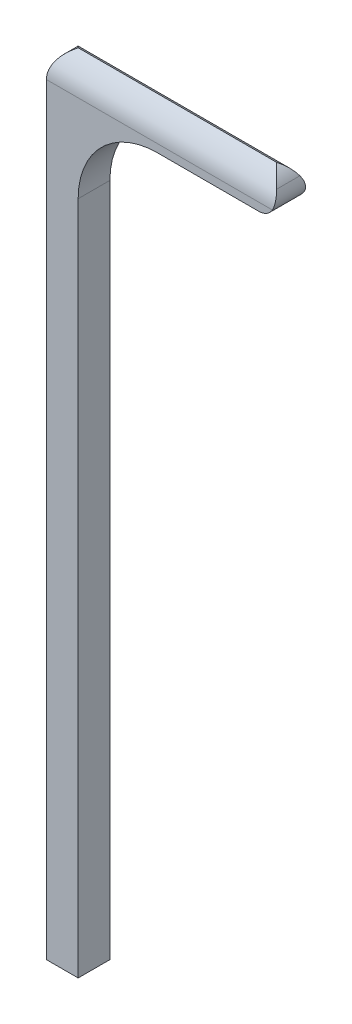
SolidWorks part; units mm, degrees
ref_plane "Front Plane" through (0, 0, 0) normal (0, 0, 1) x (1, 0, 0)
ref_plane "Top Plane" through (0, 0, 0) normal (0, 1, 0) x (1, 0, 0)
ref_plane "Right Plane" through (0, 0, 0) normal (1, 0, 0) x (0, 0, -1)
sketch "Sketch1" plane through (0, 0, 0) normal (0, 1, 0) x (1, 0, 0)
  line L1 (0, 0) -> (4, 0)
  line L2 (0, 0) -> (0, 4)
  line L3 (0, 4) -> (4, 4)
  line L4 (4, 0) -> (4, 4)
  dimension "D1" = 4
extrude "Boss-Extrude1" add sketch "Sketch1" along normal blind 100
sketch "Sketch2" plane through (4, 0, 0) normal (1, 0, 0) x (0, 0, -1)
  line L0 (0, 100) -> (0, 0) construction
  line L1 (4, 100) -> (0, 100)
  line L2 (4, 100) -> (4, 95)
  line L3 (4, 95) -> (0, 95)
  line L4 (0, 100) -> (0, 95)
  dimension "D1" = 5
extrude "Boss-Extrude2" add sketch "Sketch2" along normal blind 25
fillet "Fillet1" radius 10 1 edges at (4, 95, -2)
fillet "Fillet3" radius 4 4 edges at (14.5, 100, -4) (29, 100, -2) (14.5, 100, 0) (0, 100, -2)
fillet "Fillet4" radius 2 1 edges at (29, 95, -2)
